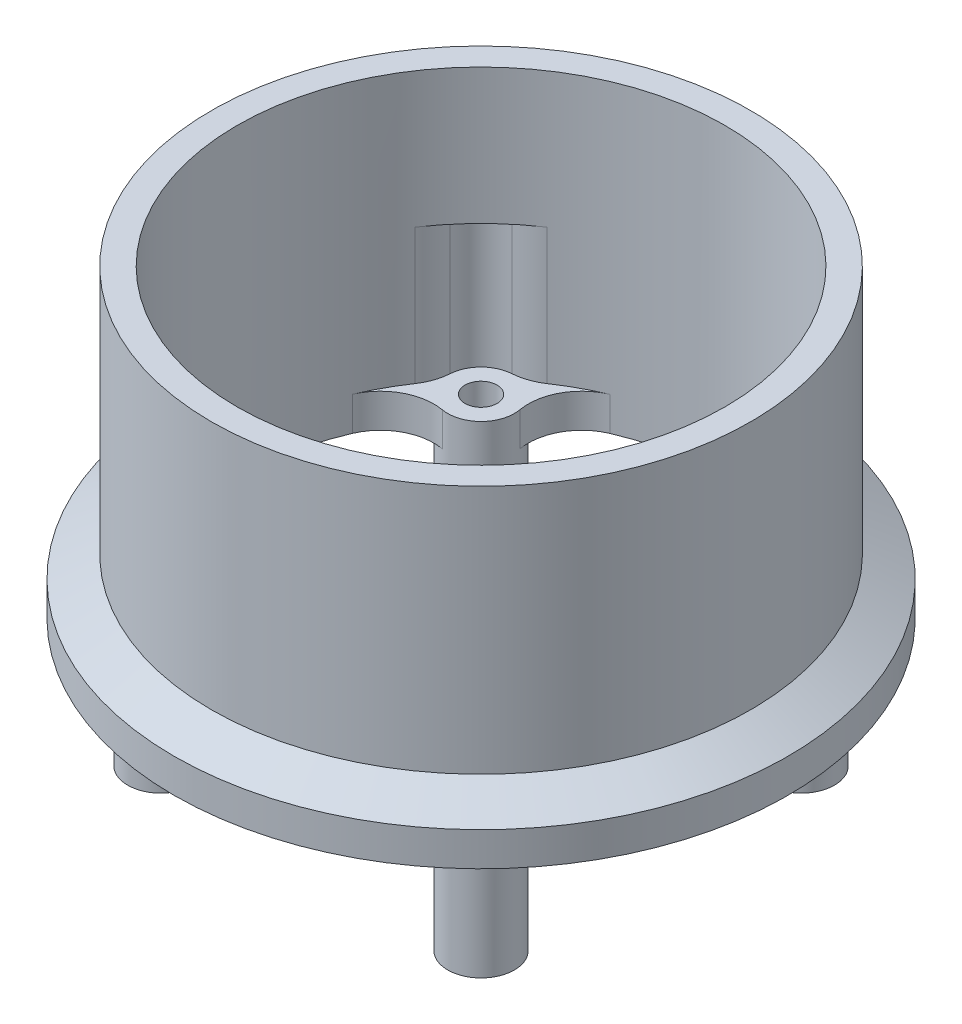
SolidWorks part; units mm, degrees
ref_plane "Front Plane" through (0, 0, 0) normal (0, 0, 1) x (1, 0, 0)
ref_plane "Top Plane" through (0, 0, 0) normal (0, 1, 0) x (1, 0, 0)
ref_plane "Right Plane" through (0, 0, 0) normal (1, 0, 0) x (0, 0, -1)
sketch "Sketch1" plane through (0, 0, 0) normal (0, 1, 0) x (1, 0, 0)
  circle A2 centre (0, 0) radius 25.273
  circle A3 centre (0, 0) radius 22.86
extrude "Boss-Extrude1" add sketch "Sketch1" along normal blind 25.4
sketch "Sketch3" plane through (0, 0, 0) normal (0, -1, 0) x (-1, 0, 0)
  line L0 (-19, -19) -> (-19, 19)
  line L2 (-19, -19) -> (19, -19)
  line L3 (19, -19) -> (19, 19)
  line L4 (19, 19) -> (-19, 19)
  circle A0 centre (15, -15) radius 1.25
  circle A1 centre (-15, -15) radius 1.25
  circle A2 centre (-15, 15) radius 1.25
  circle A3 centre (15, 15) radius 1.25
  dimension "D1" = 38
  dimension "D3" = 2.5
  dimension "D2" = 38
ref_plane "Plane1" through (0, 12.7, 0) normal (0, 1, 0) x (1, 0, 0)
sketch "Sketch5" plane through (0, 12.7, 0) normal (0, 1, 0) x (1, 0, 0)
  circle A0 centre (-15, 15) radius 3.125
  circle A1 centre (15, 15) radius 3.125
  circle A2 centre (15, -15) radius 3.125
  circle A3 centre (-15, -15) radius 3.125
sketch "Sketch6" plane through (0, 0, 0) normal (0, -1, 0) x (1, 0, 0)
  circle A0 centre (-15, 15) radius 3.125
  circle A1 centre (-15, -15) radius 3.125
  circle A2 centre (15, -15) radius 3.125
  circle A3 centre (15, 15) radius 3.125
extrude "Boss-Extrude2" add sketch "Sketch6" along normal blind 3.175
extrude "Cut-Extrude1" cut sketch "Sketch5" against normal up to surface (12.7 mm away) up to face at (0, 0, 0)
sketch "Sketch10" plane through (0, 0, 0) normal (0, -1, 0) x (1, 0, 0)
  circle A0 centre (0, 0) radius 25.273 construction
  circle A1 centre (0, 0) radius 25.273
  arc A2 (-17.9929, 14.1009) -> (-17.9929, -14.1009) centre (0, 0) ccw construction
  arc A3 (-17.9929, 14.1009) -> (-17.9929, -14.1009) centre (0, 0) ccw
  arc A4 (17.9929, 14.1009) -> (14.1009, 17.9929) centre (15, 15) ccw construction
  arc A5 (-14.1009, 17.9929) -> (-17.9929, 14.1009) centre (-15, 15) ccw construction
  arc A6 (14.1009, 17.9929) -> (-14.1009, 17.9929) centre (0, 0) ccw construction
  arc A7 (17.9929, -14.1009) -> (17.9929, 14.1009) centre (0, 0) ccw construction
  arc A8 (17.9929, 14.1009) -> (14.1009, 17.9929) centre (15, 15) ccw
  arc A9 (-14.1009, 17.9929) -> (-17.9929, 14.1009) centre (-15, 15) ccw
  arc A10 (14.1009, 17.9929) -> (-14.1009, 17.9929) centre (0, 0) ccw
  arc A11 (17.9929, -14.1009) -> (17.9929, 14.1009) centre (0, 0) ccw
  arc A12 (-17.9929, -14.1009) -> (-14.1009, -17.9929) centre (-15, -15) ccw construction
  arc A13 (-14.1009, -17.9929) -> (14.1009, -17.9929) centre (0, 0) ccw construction
  arc A14 (14.1009, -17.9929) -> (17.9929, -14.1009) centre (15, -15) ccw construction
  arc A15 (-17.9929, -14.1009) -> (-14.1009, -17.9929) centre (-15, -15) ccw
  arc A16 (-14.1009, -17.9929) -> (14.1009, -17.9929) centre (0, 0) ccw
  arc A17 (14.1009, -17.9929) -> (17.9929, -14.1009) centre (15, -15) ccw
extrude "Boss-Extrude3" add sketch "Sketch10" along normal up to surface (3.175 mm away) up to face at (-15, -3.175, 11.875)
extrude "Cut-Extrude2" cut sketch "Sketch3" against normal through all both and the other way through all contours A2 | A3 | A0 | A1 region at (-15, 0, 15) region at (15, 0, -15) region at (-15, 0, -15)
fillet "Fillet1" radius 5 8 edges at (14.1009, -1.5875, 17.9929) (17.9929, -1.5875, 14.1009) (17.9929, -1.5875, -14.1009) (14.1009, -1.5875, -17.9929) (-17.9929, -1.5875, -14.1009) (-14.1009, -1.5875, -17.9929) (-14.1009, -1.5875, 17.9929) (-17.9929, -1.5875, 14.1009)
fillet "Fillet3" radius 5 8 edges at (-14.1009, 6.35, 17.9929) (-17.9929, 6.35, 14.1009) (-17.9929, 6.35, -14.1009) (-14.1009, 6.35, -17.9929) (14.1009, 6.35, -17.9929) (17.9929, 6.35, -14.1009) (17.9929, 6.35, 14.1009) (14.1009, 6.35, 17.9929)
sketch "Sketch11" plane through (0, -3.175, 0) normal (0, -1, 0) x (1, 0, 0)
  line L0 (0, 0) -> (0, 26.4166)
  line L1 (0, 0) -> (27.5291, 0)
  circle A0 centre (-15, 15) radius 1.25
  circle A1 centre (-15, 15) radius 3.125
  circle A2 centre (15, 15) radius 3.125
  circle A3 centre (15, 15) radius 1.25
  circle A4 centre (15, -15) radius 3.125
  circle A5 centre (15, -15) radius 1.25
  circle A6 centre (-15, -15) radius 1.25
  circle A7 centre (-15, -15) radius 3.125
  circle M6 centre (-15, -15) radius 1.25
  circle M7 centre (15, -15) radius 1.25
  arc M10 (-15.5501, 11.9238) -> (-11.9238, 15.5501) centre (-15, 15) ccw
  arc M14 (11.9238, 15.5501) -> (15.5501, 11.9238) centre (15, 15) ccw
  arc M18 (15.5501, -11.9238) -> (11.9238, -15.5501) centre (15, -15) ccw
  arc M22 (-11.9238, -15.5501) -> (-15.5501, -11.9238) centre (-15, -15) ccw
  circle M25 centre (-15, 15) radius 1.25
  circle M26 centre (15, 15) radius 1.25
extrude "Boss-Extrude4" add sketch "Sketch11" along normal blind 12 contours A1 M10 M25 | A2 M14 M26 | A4 M18 M7 | A7 M22 M6 region at (-13.0509, -3.175, 12.6715) region at (17.3285, -3.175, 13.0509) region at (15.2683, -3.175, -18.0247) region at (-11.9753, -3.175, -15.2683)
sketch "Sketch13" plane through (0, -15.175, 0) normal (0, -1, 0) x (1, 0, 0)
  circle A0 centre (-15, 15) radius 1.5
  circle A1 centre (15, 15) radius 1.5
  circle A2 centre (15, -15) radius 1.5
  circle A3 centre (-15, -15) radius 1.5
extrude "Cut-Extrude3" cut sketch "Sketch13" against normal through all
sketch "Sketch14" plane through (0, 0, 0) normal (1, 0, 0) x (0, 0, -1)
  line L0 (-25.273, 25.4) -> (-25.273, 0)
  line L1 (-25.273, 25.4) -> (-25.273, -3.175) construction
  line L2 (-25.273, 0) -> (-28.773, 0)
  line L3 (-25.273, -3.175) -> (-28.773, -3.175)
  line L4 (-28.773, -3.175) -> (-28.773, 0)
  line L5 (-25.273, 0) -> (-25.273, -3.175)
  line L6 (-25.273, 25.4) -> (25.273, 25.4)
  line L7 (0, 25.4) -> (0, -11.3041)
revolve "Revolve1" add sketch "Sketch14" angle 360 about L7 region at (0, -1.5875, 27.023)
chamfer "Chamfer1" distance 3.5 angle 30 1 edges at (0, 0, 25.273) first distance on face at (0, 0, 28.773)
